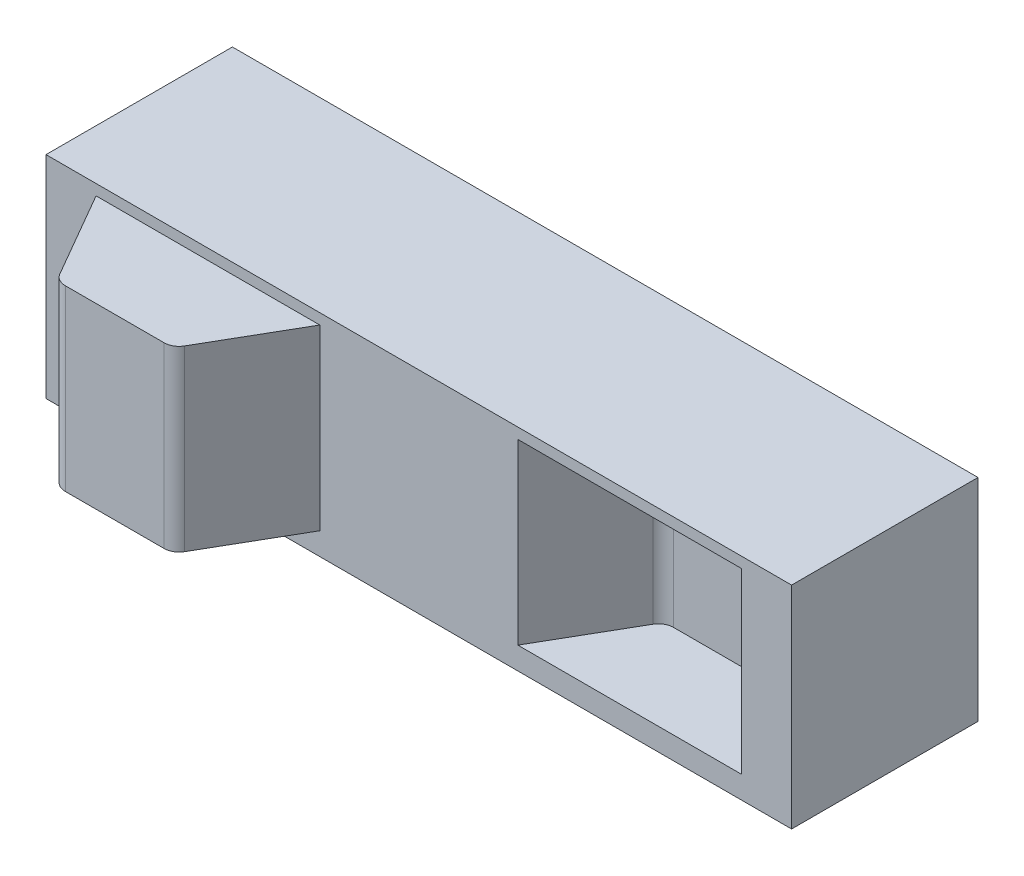
SolidWorks part; units mm, degrees
ref_plane "Front" through (0, 0, 0) normal (0, 0, 1) x (1, 0, 0)
ref_plane "Top" through (0, 0, 0) normal (0, 1, 0) x (1, 0, 0)
ref_plane "Right" through (0, 0, 0) normal (1, 0, 0) x (0, 0, -1)
sketch "Sketch1" plane through (0, 0, 0) normal (0, 1, 0) x (1, 0, 0)
  line L0 (-50, 0) -> (50, 0)
  line L1 (-50, 0) -> (-50, 25)
  line L2 (-50, 25) -> (50, 25)
  line L3 (50, 25) -> (50, 0)
  dimension "D1" = 100
  dimension "D2" = 25
extrude "Boss-Extrude1" add sketch "Sketch1" along normal mid plane 28.335
sketch "Sketch2" plane through (0, 0, 0) normal (0, 1, 0) x (1, 0, 0)
  line L1 (-28.2833, 0) -> (-28.2833, -12.5) construction
  line L2 (-50, 0) -> (50, 0) construction
  line L3 (13.2833, 0) -> (43.2833, 0)
  line L4 (43.2833, 0) -> (36.0665, 12.5)
  line L5 (36.0665, 12.5) -> (20.5002, 12.5)
  line L6 (-20.5002, -12.5) -> (-36.0665, -12.5)
  line L8 (-20.5002, -12.5) -> (-13.2833, 0)
  line L10 (-36.0665, -12.5) -> (-43.2833, 0)
  line L12 (-43.2833, 0) -> (-13.2833, 0)
  line L13 (20.5002, 12.5) -> (13.2833, 0)
  line L14 (28.2833, 12.5) -> (28.2833, 0) construction
  line L15 (0, 0) -> (0, 25) construction
  line L16 (50, 25) -> (-50, 25) construction
  point P9 (-28.2833, -12.5)
  point P19 (0, 0)
  point P20 (-24.0514, 0)
  point P21 (30.4529, 12.5)
  point P22 (-26.6943, 0)
  dimension "D1" = 60
  dimension "D2" = 12.5
  dimension "D3" = 30
  dimension "D4" = 56.5667
extrude "Boss-Extrude2" add sketch "Sketch2" along normal offset from surface 1.435 and the other way offset from surface 3 contours L12 L10 L6 L8 region at (-28.2833, 0, 5.5901) up to face at (0, 14.1675, -12.5) other way up to face at (0, -14.1675, -12.5)
fillet "Fillet1" radius 2 2 edges at (-36.0665, 0.7825, 12.5) (-20.5002, 0.7825, 12.5)
extrude "Cut-Extrude1" cut sketch "Sketch2<3>" against normal offset from surface 3 and the other way offset from surface 1.435 contours L5 L13 L3 L4 region at (28.2833, 0, -5.5901) up to face at (0, -14.1675, -12.5) other way up to face at (0, 14.1675, -12.5)
sketch "Sketch2<3>" plane through (0, 0, 0) normal (0, 1, 0) x (1, 0, 0) same geometry as "Sketch2"
fillet "Fillet2" radius 2 2 edges at (36.0665, 0.7825, -12.5) (20.5002, 0.7825, -12.5)
